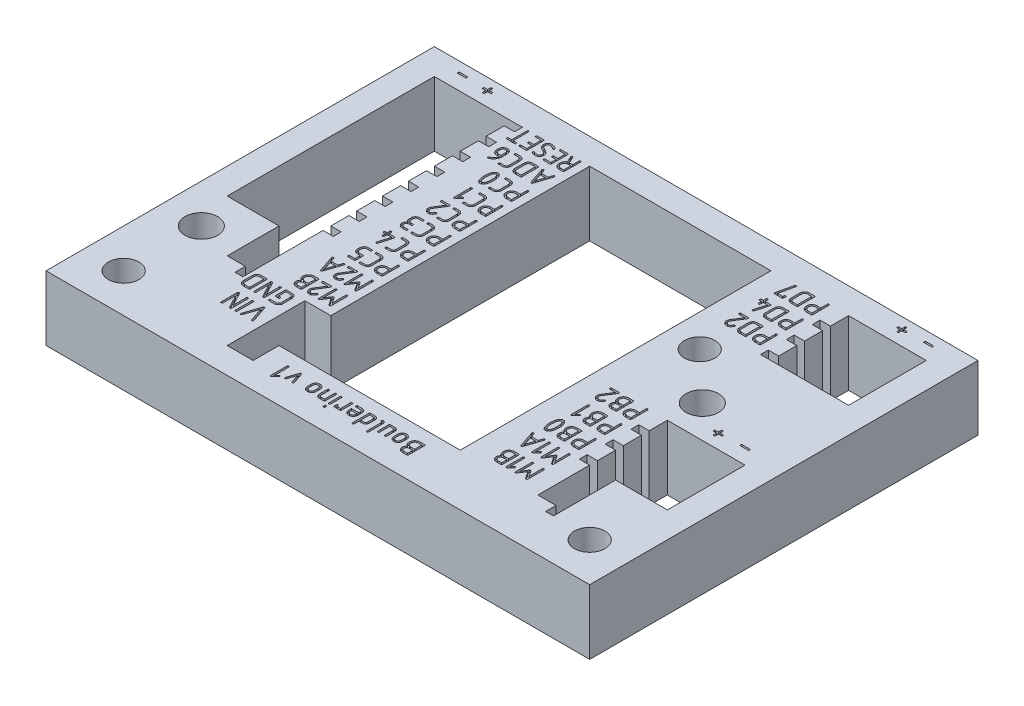
SolidWorks part; units mm, degrees
material "Acrylic (Medium-high impact)"
ref_plane "Front Plane" through (0, 0, 0) normal (0, 0, 1) x (1, 0, 0)
ref_plane "Top Plane" through (0, 0, 0) normal (0, 1, 0) x (1, 0, 0)
ref_plane "Right Plane" through (0, 0, 0) normal (1, 0, 0) x (0, 0, -1)
sketch "Sketch1" plane through (0, 0, 0) normal (0, 1, 0) x (-1, 0, 0)
  line L0 (-16.51, 13.97) -> (-16.51, 1.27)
  line L1 (16.51, 8.89) -> (16.51, -16.51)
  line L2 (-26.67, 19.05) -> (-26.67, -19.05)
  line L3 (-26.67, 19.05) -> (26.67, 19.05)
  line L4 (26.67, 19.05) -> (26.67, -19.05)
  line L5 (-24.13, -16.51) -> (-16.51, -16.51)
  line L6 (-24.13, -16.51) -> (-24.13, -8.89)
  line L7 (-24.13, 8.89) -> (-19.05, 8.89)
  line L8 (-8.89, -16.51) -> (-8.89, 13.97)
  line L9 (16.51, -16.51) -> (24.13, -16.51)
  line L10 (-8.89, 13.97) -> (8.89, 13.97)
  line L11 (-16.51, 13.97) -> (-19.05, 13.97)
  line L12 (-19.05, 8.89) -> (-19.05, 13.97)
  line L13 (-26.67, -19.05) -> (26.67, -19.05)
  line L14 (19.05, 3.81) -> (24.13, 3.81)
  line L15 (24.13, -16.51) -> (24.13, 3.81)
  line L16 (11.43, 16.51) -> (11.43, 8.89)
  line L17 (-24.13, 1.27) -> (-16.51, 1.27)
  line L18 (16.51, 8.89) -> (19.05, 8.89)
  line L19 (19.05, 3.81) -> (19.05, 8.89)
  line L23 (-24.13, -8.89) -> (-16.51, -8.89)
  line L24 (-24.13, 1.27) -> (-24.13, 8.89)
  line L25 (-16.51, -8.89) -> (-16.51, -16.51)
  line L26 (11.43, 8.89) -> (8.89, 8.89)
  line L27 (11.43, 16.51) -> (8.89, 16.51)
  line L28 (8.89, 8.89) -> (8.89, -16.51)
  line L29 (8.89, 13.97) -> (8.89, 16.51)
  line L30 (-8.89, -1.27) -> (-13.0889, -1.27) construction
  line L31 (-8.89, -16.51) -> (8.89, -16.51)
  line L32 (-26.67, 19.05) -> (26.67, -19.05) construction
  circle A0 centre (-22.86, 15.24) radius 1.5
  circle A1 centre (22.86, 15.24) radius 1.5
  circle A2 centre (-12.065, -6.35) radius 1.5
  circle A3 centre (22.86, 7.62) radius 1.6
  circle A4 centre (-16.764, -1.905) radius 1.6
  dimension "D18" = 3
  dimension "D25" = 3.2
  dimension "D3" = 2.54
  dimension "D4" = 53.34
  dimension "D5" = 2.54
  dimension "D6" = 7.62
  dimension "D7" = 7.62
  dimension "D8" = 25.4
  dimension "D9" = 2.54
  dimension "D10" = 2.54
  dimension "D11" = 30.48
  dimension "D12" = 25.4
  dimension "D13" = 10.16
  dimension "D14" = 7.62
  dimension "D15" = 3.81
  dimension "D16" = 3.81
  dimension "D17" = 38.1
  dimension "D19" = 11.43
  dimension "D20" = 3.81
  dimension "D21" = 5.08
  dimension "D22" = 3.81
  dimension "D23" = 20.955
  dimension "D24" = 14.605
  dimension "D26" = 25.4
  dimension "D27" = 3.81
  dimension "D28" = 9.906
  dimension "D29" = 5.08
  dimension "D30" = 5.08
  dimension "D31" = 17.78
  dimension "D32" = 2.54
  dimension "D33" = 2.54
  dimension "D34" = 8.89
  dimension "D35" = 2.54
  dimension "D36" = 25.4
  dimension "D37" = 2.54
extrude "Boss-Extrude1" add sketch "Sketch1" along normal blind 6.35
sketch "Sketch3" plane through (0, 6.35, 0) normal (0, 1, 0) x (1, 0, 0)
  line L1 (19.05, -13.97) -> (18.288, -13.97)
  line L2 (19.05, -13.97) -> (19.05, -14.986)
  line L3 (19.05, -14.986) -> (18.288, -14.986)
  line L4 (18.288, -13.97) -> (18.288, -14.986)
  dimension "D1" = 0.762
  dimension "D2" = 1.016
extrude "Cut-Extrude1" cut sketch "Sketch3" against normal through all
sketch "Sketch6" plane through (0, 6.35, 0) normal (0, 1, 0) x (1, 0, 0)
  line L0 (16.51, -1.27) -> (16.51, -13.97) construction
  line L1 (16.51, -8.89) -> (15.494, -8.89)
  line L2 (16.51, -8.89) -> (16.51, -8.128)
  line L3 (16.51, -8.128) -> (15.494, -8.128)
  line L4 (15.494, -8.89) -> (15.494, -8.128)
  line L5 (-26.67, -19.05) -> (26.67, -19.05) construction
  dimension "D1" = 1.016
  dimension "D2" = 0.762
  dimension "D3" = 10.16
extrude "Cut-Extrude2" cut sketch "Sketch6" against normal through all
pattern_linear "LPattern1" count 10 spacing 2.54 along (0, 0, -1) skipping (3, 0), (4, 0), (5, 0), (6, 0) of "Cut-Extrude2"
sketch "Sketch7" plane through (0, 6.35, 0) normal (0, 1, 0) x (1, 0, 0)
  line L1 (-16.51, -8.89) -> (-17.272, -8.89)
  line L2 (-16.51, -8.89) -> (-16.51, -9.906)
  line L3 (-16.51, -9.906) -> (-17.272, -9.906)
  line L4 (-17.272, -8.89) -> (-17.272, -9.906)
  dimension "D1" = 0.762
  dimension "D2" = 1.016
extrude "Cut-Extrude3" cut sketch "Sketch7" against normal through all
sketch "Sketch8" plane through (0, 6.35, 0) normal (0, 1, 0) x (1, 0, 0)
  line L1 (-16.51, 16.51) -> (-15.494, 16.51)
  line L2 (-16.51, 16.51) -> (-16.51, 15.748)
  line L3 (-16.51, 15.748) -> (-15.494, 15.748)
  line L4 (-15.494, 16.51) -> (-15.494, 15.748)
  dimension "D1" = 0.762
  dimension "D2" = 1.016
extrude "Cut-Extrude4" cut sketch "Sketch8" against normal through all
pattern_linear "LPattern2" count 8 spacing 2.54 along (0, 0, 1) of "Cut-Extrude4"
sketch "Sketch10" plane through (0, 6.35, 0) normal (0, 1, 0) x (1, 0, 0)
  line L0 (14.859, -19.05) -> (14.859, 19.05) construction
  line L1 (-26.67, -19.05) -> (26.67, -19.05) construction
  line L2 (26.67, 19.05) -> (-26.67, 19.05) construction
  line L3 (15.494, -8.128) -> (15.494, -8.89) construction
  line L4 (-12.065, -19.05) -> (-12.065, -8.89) construction
  line L5 (-11.43, -8.89) -> (-11.43, -16.51) construction
  line L6 (-9.525, -19.05) -> (-9.525, 19.05) construction
  line L7 (-8.89, 16.51) -> (-8.89, -8.89) construction
  line L8 (23.9093, 0.762) -> (21.3693, 0.762) construction
  line L9 (21.3693, 0.762) -> (18.8293, 0.762) construction
  line L10 (24.13, -1.27) -> (16.51, -1.27) construction
  line L11 (24.13, 18.542) -> (21.59, 18.542) construction
  line L12 (21.59, 18.542) -> (19.05, 18.542) construction
  line L13 (-19.05, 18.542) -> (-21.59, 18.542) construction
  line L14 (-21.59, 18.542) -> (-24.13, 18.542) construction
  line L15 (24.13, 16.51) -> (16.51, 16.51) construction
  line L16 (24.13, 8.89) -> (24.13, 16.51) construction
  line L18 (14.859, -11.43) -> (8.89, -11.43) construction
  line L21 (8.89, -13.97) -> (8.89, 16.51) construction
  line L22 (14.859, -8.89) -> (8.89, -8.89) construction
  line L23 (14.859, -6.35) -> (8.89, -6.35) construction
  line L24 (14.859, -3.81) -> (8.89, -3.81) construction
  line L25 (14.859, -1.27) -> (8.89, -1.27) construction
  line L26 (14.859, 1.27) -> (8.89, 1.27) construction
  line L27 (14.859, 3.81) -> (8.89, 3.81) construction
  line L28 (14.859, 6.35) -> (8.89, 6.35) construction
  line L29 (14.859, 8.89) -> (8.89, 8.89) construction
  line L30 (-12.065, -11.43) -> (-26.67, -11.43) construction
  line L31 (-26.67, 19.05) -> (-26.67, -19.05) construction
  line L32 (-8.89, -13.97) -> (8.89, -13.97) construction
  line L33 (-12.065, -8.89) -> (-26.67, -8.89) construction
  line L34 (-9.525, -6.35) -> (-16.51, -6.35) construction
  line L35 (-16.51, -9.906) -> (-16.51, -2.032) construction
  line L36 (-9.525, -3.81) -> (-16.51, -3.81) construction
  line L37 (-9.525, -1.27) -> (-16.51, -1.27) construction
  line L38 (-9.525, 1.27) -> (-16.51, 1.27) construction
  line L39 (-9.525, 3.81) -> (-16.51, 3.81) construction
  line L40 (-9.525, 6.35) -> (-16.51, 6.35) construction
  line L41 (-9.525, 8.89) -> (-16.51, 8.89) construction
  line L42 (-9.525, 11.43) -> (-16.51, 11.43) construction
  line L43 (-9.525, 13.97) -> (-16.51, 13.97) construction
  line L44 (-9.525, 16.51) -> (-16.51, 16.51) construction
  line L45 (14.859, 11.43) -> (8.89, 11.43) construction
  line L46 (14.859, 13.97) -> (8.89, 13.97) construction
  line L47 (14.859, 16.51) -> (8.89, 16.51) construction
  line L48 (-24.13, 16.51) -> (-24.13, -3.81) construction
  line L51 (8.89, -19.05) -> (8.89, -13.97) construction
  line L52 (-8.89, -13.97) -> (-8.89, -19.05) construction
  line L53 (8.89, -15.24) -> (-8.89, -15.24) construction
  text T0 "M1B\r\n"
  text T1 "M1A"
  text T2 "PB0\r\n"
  text T3 "PB1"
  text T4 "PB2"
  text T5 "PD2"
  text T6 "PD4"
  text T7 "PD7"
  text T8 "VIN"
  text T9 "GND"
  text T10 "M2B"
  text T11 "M2A"
  text T12 "PC5"
  text T13 "PC4"
  text T14 "PC3"
  text T15 "PC2"
  text T16 "PC1"
  text T17 "PC0"
  text T18 "ADC6"
  text T19 "RESET" font "GOST Common" height in points 7
  text T20 "-"
  text T21 "+"
  text T22 "-"
  text T23 "+"
  text T24 "+"
  text T25 "-"
  text T26 "Boulderino v1"
  dimension "D1" = 0.635
  dimension "D2" = 0.635
  dimension "D3" = 0.635
  dimension "D4" = 2.032
  dimension "D5" = 2.54
  dimension "D6" = 2.032
  dimension "D8" = 2.54
  dimension "D9" = 2
  dimension "D10" = 10
  dimension "D7" = 12
extrude "Cut-Extrude5" cut sketch "Sketch10" against normal blind 0.254
